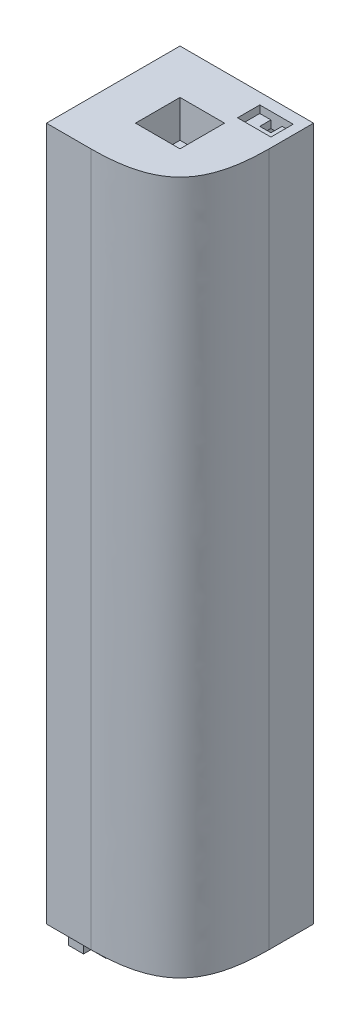
SolidWorks part; units mm, degrees
ref_plane "Front Plane" through (0, 0, 0) normal (0, 0, 1) x (1, 0, 0)
ref_plane "Top Plane" through (0, 0, 0) normal (0, 1, 0) x (1, 0, 0)
ref_plane "Right Plane" through (0, 0, 0) normal (1, 0, 0) x (0, 0, -1)
sketch "Sketch1" plane through (0, 0, 0) normal (0, 1, 0) x (1, 0, 0)
  line L1 (0, 0) -> (36, 0)
  line L2 (0, 0) -> (0, 36)
  line L3 (0, 36) -> (36, 36)
  line L4 (36, 0) -> (36, 36)
  dimension "D1" = 36
  dimension "D2" = 36
extrude "Boss-Extrude1" add sketch "Sketch1" along normal blind 186.9
fillet "Fillet1" radius 24 1 edges at (36, 93.45, 0) conic rho 0.55
sketch "Sketch2" plane through (0, 0, 0) normal (0, -1, 0) x (1, 0, 0)
  line L0 (36, -24) -> (36, -36) construction
  line L1 (0, -12.5) -> (14.28, -12.5)
  line L2 (0, -12.5) -> (0, -36)
  line L3 (0, -36) -> (14.28, -36)
  line L4 (14.28, -12.5) -> (14.28, -36)
  line L5 (0, 0) -> (12, 0) construction
  line L6 (0, -36) -> (0, 0) construction
  line L7 (36, -36) -> (0, -36) construction
  dimension "D1" = 21.72
  dimension "D2" = 12.5
  dimension "D3" = 0
  dimension "D4" = 0
extrude "Cut-Extrude1" cut sketch "Sketch2" against normal blind 27
sketch "Sketch3" plane through (0, 27, 0) normal (0, -1, 0) x (1, 0, 0)
  line L0 (0, -12.5) -> (0, -36) construction
  line L1 (0, -15) -> (11.78, -15)
  line L2 (0, -15) -> (0, -36)
  line L3 (0, -36) -> (11.78, -36)
  line L4 (11.78, -15) -> (11.78, -36)
  line L5 (0, -36) -> (14.28, -36) construction
  line L6 (14.28, -12.5) -> (0, -12.5) construction
  line L7 (14.28, -36) -> (14.28, -12.5) construction
  dimension "D1" = 2.5
  dimension "D2" = 2.5
extrude "Cut-Extrude2" cut sketch "Sketch3" against normal blind 8
sketch "Sketch4" plane through (0, 0, 0) normal (0, -1, 0) x (1, 0, 0)
  line L0 (36, -24) -> (36, -36) construction
  line L1 (0, 0) -> (12, 0) construction
  circle A0 centre (21, -15) radius 2
  dimension "D1" = 4
  dimension "D2" = 15
  dimension "D3" = 15
extrude "Cut-Extrude3" cut sketch "Sketch4" against normal blind 5
sketch "Sketch5" plane through (0, 0, 0) normal (0, -1, 0) x (1, 0, 0)
  line L0 (36, -24) -> (36, -36) construction
  line L1 (18.28, -28) -> (22.28, -28)
  line L2 (18.28, -28) -> (18.28, -32)
  line L3 (18.28, -32) -> (32, -32)
  line L4 (32, -28) -> (32, -32)
  line L5 (36, -36) -> (14.28, -36) construction
  line L6 (14.28, -36) -> (14.28, -12.5) construction
  line L7 (0, 0) -> (12, 0) construction
  line L8 (4, -2) -> (8, -2)
  line L9 (4, -2) -> (4, -10.5)
  line L10 (4, -10.5) -> (8, -10.5)
  line L11 (8, -2) -> (8, -4)
  line L12 (14.28, -12.5) -> (0, -12.5) construction
  line L13 (0, -12.5) -> (0, 0) construction
  line L14 (8, -8.5) -> (8, -10.5)
  line L15 (8, -4) -> (12, -4)
  line L17 (8, -8.5) -> (12, -8.5)
  line L18 (12, -4) -> (12, -8.5)
  line L20 (22.28, -28) -> (22.28, -24)
  line L21 (22.28, -24) -> (28, -24)
  line L22 (28, -28) -> (28, -24)
  line L23 (28, -28) -> (32, -28)
  dimension "D1" = 4
  dimension "D2" = 4
  dimension "D3" = 4
  dimension "D4" = 4
  dimension "D5" = 2
  dimension "D6" = 2
  dimension "D7" = 4
  dimension "D8" = 4
  dimension "D9" = 2
  dimension "D10" = 2
  dimension "D11" = 4
  dimension "D12" = 4
  dimension "D13" = 4
  dimension "D14" = 4
  dimension "D15" = 24
  dimension "D16" = 24
extrude "Boss-Extrude2" add sketch "Sketch5" along normal blind 4
sketch "Sketch6" plane through (0, 0, -36) normal (0, 0, -1) x (-1, 0, 0)
  line L0 (-36, 186.9) -> (0, 186.9) construction
  line L1 (-32, 182.9) -> (-26, 182.9)
  line L2 (-32, 182.9) -> (-32, 178.9)
  line L3 (-32, 178.9) -> (-26, 178.9)
  line L4 (-26, 182.9) -> (-26, 178.9)
  line L5 (-36, 186.9) -> (-36, 0) construction
  line L6 (0, 186.9) -> (0, 35) construction
  line L7 (-10, 182.9) -> (-4, 182.9)
  line L8 (-10, 182.9) -> (-10, 178.9)
  line L9 (-10, 178.9) -> (-4, 178.9)
  line L10 (-4, 182.9) -> (-4, 178.9)
  line L12 (-32, 162.9) -> (-26, 162.9)
  line L13 (-32, 162.9) -> (-32, 158.9)
  line L14 (-32, 158.9) -> (-26, 158.9)
  line L15 (-26, 162.9) -> (-26, 158.9)
  dimension "D1" = 4
  dimension "D2" = 4
  dimension "D3" = 6
  dimension "D4" = 4
  dimension "D5" = 6
  dimension "D6" = 4
  dimension "D7" = 4
  dimension "D8" = 4
  dimension "D9" = 16
  dimension "D10" = 4
extrude "Cut-Extrude4" cut sketch "Sketch6" against normal blind 9
sketch "Sketch7" plane through (0, 186.9, 0) normal (0, 1, 0) x (1, 0, 0)
  line L0 (36, 36) -> (0, 36) construction
  line L1 (27.5, 33) -> (30.5, 33)
  line L2 (27.5, 33) -> (27.5, 30)
  line L3 (27.5, 30) -> (30.5, 30)
  line L4 (30.5, 33) -> (30.5, 30)
  line L5 (36, 24) -> (36, 36) construction
  line L6 (0, 0) -> (12, 0) construction
  line L7 (12, 24) -> (24, 24)
  line L8 (12, 24) -> (12, 12)
  line L9 (12, 12) -> (24, 12)
  line L10 (24, 24) -> (24, 12)
  dimension "D1" = 3
  dimension "D2" = 3
  dimension "D3" = 3
  dimension "D4" = 5.5
  dimension "D5" = 12
  dimension "D6" = 12
  dimension "D7" = 12
  dimension "D8" = 12
extrude "Cut-Extrude5" cut sketch "Sketch7" against normal blind 10
sketch "Sketch8" plane through (0, 186.9, 0) normal (0, 1, 0) x (1, 0, 0)
  line L0 (30.5, 33) -> (27.5, 33) construction
  line L1 (33.5, 33) -> (24.5, 33)
  line L2 (33.5, 33) -> (33.5, 27)
  line L3 (33.5, 27) -> (24.5, 27)
  line L4 (24.5, 33) -> (24.5, 27)
  line L5 (30.5, 30) -> (30.5, 33) construction
  line L6 (27.5, 33) -> (27.5, 30) construction
  line L7 (27.5, 30) -> (30.5, 30) construction
  dimension "D1" = 0
  dimension "D2" = 3
  dimension "D3" = 3
  dimension "D4" = 3
extrude "Cut-Extrude6" cut sketch "Sketch8" against normal blind 2
